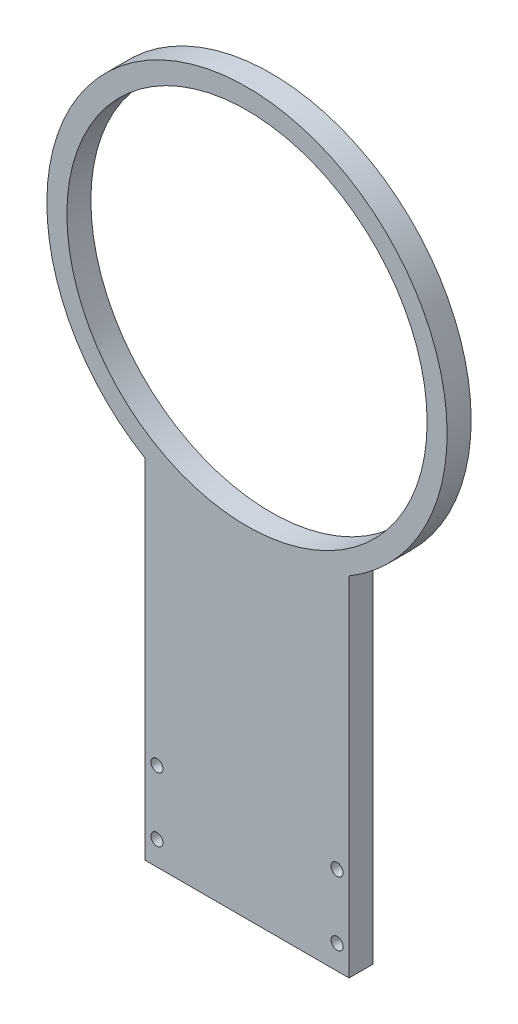
SolidWorks part; units mm, degrees
ref_plane "Front" through (0, 0, 0) normal (0, 0, 1) x (1, 0, 0)
ref_plane "Top" through (0, 0, 0) normal (0, 1, 0) x (1, 0, 0)
ref_plane "Right" through (0, 0, 0) normal (1, 0, 0) x (0, 0, -1)
sketch "Esquisse1" plane through (0, 0, 0) normal (0, 0, 1) x (1, 0, 0)
  line L1 (0, 0) -> (100, 0)
  line L2 (0, 0) -> (0, 100)
  line L3 (0, 100) -> (100, 100)
  line L4 (100, 0) -> (100, 100)
  dimension "D1" = 100
  dimension "D2" = 100
extrude "Boss.-Extru.1" add sketch "Esquisse1" along normal blind 6
sketch "Esquisse2" plane through (0, 0, 6) normal (0, 0, 1) x (1, 0, 0)
  line L1 (50, 0) -> (50, 100) construction
  line L2 (0, 0) -> (100, 0) construction
  line L3 (100, 100) -> (0, 100) construction
  circle A0 centre (50, 50) radius 45
  dimension "D1" = 90
extrude "Enlèv. mat.-Extru.1" cut sketch "Esquisse2" against normal through all
sketch "Esquisse3" plane through (0, 0, 6) normal (0, 0, 1) x (1, 0, 0)
  line L0 (100, 0) -> (100, 100) construction
  line L1 (0, 0) -> (100, 0)
  line L2 (0, 0) -> (0, -80)
  line L3 (0, -80) -> (100, -80)
  line L4 (100, 0) -> (100, -80)
  dimension "D1" = 80
extrude "Boss.-Extru.2" add sketch "Esquisse3" against normal up to vertex (6 mm away) up to point (100, 0, 0)
sketch "Esquisse4" plane through (0, 0, 6) normal (0, 0, 1) x (1, 0, 0)
  line L0 (50, -80) -> (50, -3.3563) construction
  line L1 (0, -80) -> (100, -80) construction
  line L2 (0, 100) -> (0, -80) construction
  line L3 (24.5, -80) -> (0, -80)
  line L4 (24.5, -80) -> (24.5, 0)
  line L5 (24.5, 0) -> (0, 0)
  line L6 (0, -80) -> (0, 0)
  line L7 (100, -80) -> (100, 0)
  line L8 (75.5, 0) -> (100, 0)
  line L9 (75.5, -80) -> (75.5, 0)
  line L10 (75.5, -80) -> (100, -80)
  dimension "D1" = 51
  dimension "D2" = 80
extrude "Enlèv. mat.-Extru.2" cut sketch "Esquisse4" against normal up to vertex (86 mm away) up to point (0, 100, -80)
sketch "Esquisse5" plane through (0, 0, 6) normal (0, 0, 1) x (1, 0, 0)
  line L0 (50, -80) -> (50, -10.2588) construction
  line L1 (24.5, -80) -> (75.5, -80) construction
  line L2 (27.5, -80) -> (27.5, -58) construction
  line L3 (24.5, -80) -> (24.5, 0) construction
  circle A0 centre (27.5, -58) radius 1.5
  circle A1 centre (27.5, -74) radius 1.5
  circle A2 centre (72.5, -74) radius 1.5
  circle A3 centre (72.5, -58) radius 1.5
  dimension "D1" = 16
  dimension "D2" = 6
  dimension "D4" = 3
  dimension "D3" = 3
extrude "Enlèv. mat.-Extru.3" cut sketch "Esquisse5" against normal through all
sketch "Esquisse6" plane through (0, 0, 6) normal (0, 0, 1) x (1, 0, 0)
  line L0 (75.5, 6.9913) -> (75.5, 0)
  line L1 (24.5, 0) -> (24.5, 6.9913)
  line L2 (100, 0) -> (100, 100) construction
  line L3 (24.5, 0) -> (-1, 0)
  line L4 (-1, 0) -> (-1, 101)
  line L5 (50, 50) -> (50, 80.2211) construction
  line L6 (50, 80.2211) -> (50, 101) construction
  line L7 (-1, 101) -> (101, 101)
  line L8 (100, 100) -> (0, 100) construction
  line L9 (0, 100) -> (0, 0) construction
  line L10 (75.5, 0) -> (101, 0)
  line L11 (101, 0) -> (101, 101)
  arc A0 (24.5, 6.9913) -> (75.5, 6.9913) centre (50, 50) cw
  dimension "D1" = 1
  dimension "D2" = 1
extrude "Enlèv. mat.-Extru.4" cut sketch "Esquisse6" against normal through all
